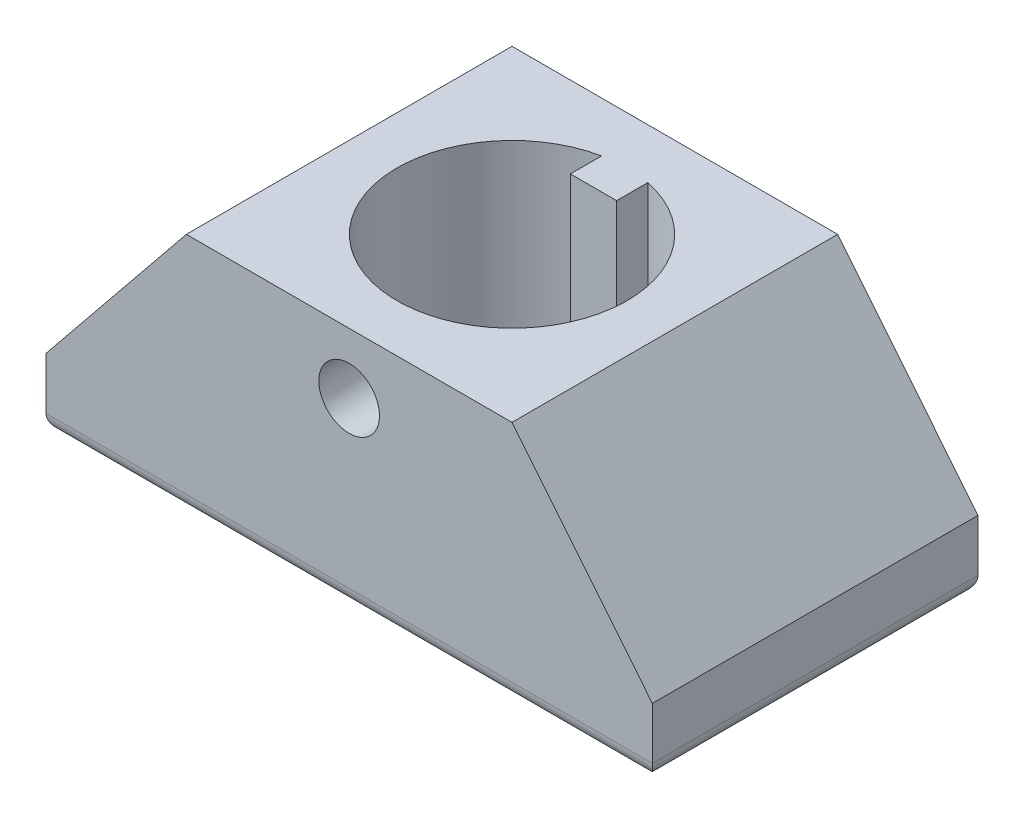
SolidWorks part; units mm, degrees
ref_plane "Front Plane" through (0, 0, 0) normal (0, 0, 1) x (1, 0, 0)
ref_plane "Top Plane" through (0, 0, 0) normal (0, 1, 0) x (1, 0, 0)
ref_plane "Right Plane" through (0, 0, 0) normal (1, 0, 0) x (0, 0, -1)
sketch "Sketch1" plane through (0, 0, 0) normal (0, 1, 0) x (1, 0, 0)
  line L0 (-1.335, 6.5044) -> (-1.335, 4.7044)
  line L1 (-1.335, 4.7044) -> (1.335, 4.7044)
  line L2 (1.335, 4.7044) -> (1.335, 6.5044)
  line L4 (-9.4, -9.4) -> (9.4, -9.4)
  line L5 (-9.4, -9.4) -> (-9.4, 9.4)
  line L6 (-9.4, 9.4) -> (9.4, 9.4)
  line L7 (9.4, -9.4) -> (9.4, 9.4)
  line L8 (-9.4, -9.4) -> (9.4, 9.4) construction
  line L9 (-9.4, 9.4) -> (9.4, -9.4) construction
  arc A1 (-1.335, 6.5044) -> (1.335, 6.5044) centre (0, 0) ccw
  dimension "D1" = 13.28
  dimension "D2" = 18.8
  dimension "D3" = 1.8
  dimension "D4" = 2.67
  dimension "D5" = 1.335
  dimension "D6" = 18.8
extrude "Boss-Extrude1" add sketch "Sketch1" along normal blind 10
sketch "Sketch5" plane through (0, 0, -4.7044) normal (0, 0, 1) x (1, 0, 0)
  line L1 (1.335, 10) -> (-1.335, 10) construction
  circle A0 centre (-0.0001, 6.5) radius 1.75
  dimension "D1" = 3.5
  dimension "D2" = 3.5
extrude "Cut-Extrude3" cut sketch "Sketch5" along normal blind 15
sketch "Sketch6" plane through (0, 0, 0) normal (0, -1, 0) x (1, 0, 0)
  line L1 (17.5, -9.4) -> (-17.5, -9.4)
  line L2 (17.5, -9.4) -> (17.5, 9.4)
  line L3 (17.5, 9.4) -> (-17.5, 9.4)
  line L4 (-17.5, -9.4) -> (-17.5, 9.4)
  line L5 (17.5, -9.4) -> (-17.5, 9.4) construction
  line L6 (17.5, 9.4) -> (-17.5, -9.4) construction
  point P0 (0, 0)
  dimension "D1" = 18.8
  dimension "D2" = 35
extrude "Boss-Extrude2" add sketch "Sketch6" along normal blind 4
sketch "Sketch7" plane through (0, 0, 9.4) normal (0, 0, 1) x (1, 0, 0)
  line L0 (-9.4, 10) -> (-9.4, 0)
  line L1 (-9.4, 0) -> (-17.5, 0)
  line L2 (-17.5, 0) -> (-9.4, 10)
  line L3 (9.4, 0) -> (17.5, 0)
  line L4 (17.5, 0) -> (9.4, 10)
  line L5 (9.4, 10) -> (9.4, 0)
extrude "Boss-Extrude3" add sketch "Sketch7" against normal up to surface (18.8 mm away) up to face at (-1.0125, 2.75, -9.4)
fillet "Fillet4" radius 1 4 edges at (17.5, -4, 0) (0, -4, -9.4) (-17.5, -4, 0) (0, -4, 9.4)
sketch "Sketch8" plane through (0, 0, 0) normal (0, 1, 0) x (1, 0, 0)
  line L0 (1.335, 4.7044) -> (-1.335, 4.7044) construction
  line L1 (1.335, 6.5044) -> (1.335, 4.7044) construction
  line L2 (-1.335, 4.7044) -> (-1.335, 6.5044) construction
  line L3 (1.335, 4.7044) -> (-1.335, 4.7044)
  line L4 (1.335, 6.5044) -> (1.335, 4.7044)
  line L5 (-1.335, 4.7044) -> (-1.335, 6.5044)
  arc A0 (-1.335, 6.5044) -> (1.335, 6.5044) centre (0, 0) ccw construction
  arc A1 (-1.335, 6.5044) -> (1.335, 6.5044) centre (0, 0) ccw
extrude "Cut-Extrude4" cut sketch "Sketch8" against normal blind 4
fillet "Fillet5" radius 0.5 4 edges at (-1.335, -4, -5.6044) (0, -4, -4.7044) (1.335, -4, -5.6044) (0, -4, 6.64)
equation "\"CageLeftBottomEdge\"=22.11mm"
equation "\"CageLeftTopEdge\"=22.11mm"
equation "\"CageRightBottomEdge\"=21.63mm"
equation "\"CageRightTopEdge\"=21.63mm"
equation "\"CageHeight\"=86.04mm"
equation "\"CageLength\"=73.76mm"
equation "\"CageTopScrewClearance\"=10mm"
equation "\"CageBottomScrewClearance\"=25mm"
equation "\"CageLeftTopDepth\"= 11.65mm"
equation "\"CageLeftBottomDepth\"=11.11mm"
equation "\"CageLeftTopHeight\"=8.56175mm"
equation "\"CageLeftBottomHeight\"=16mm"
equation "\"CageRightTopDepth\"= 11.05mm"
equation "\"CageRightBottomDepth\"=10.58mm"
equation "\"CageRightTopHeight\"=9.6mm"
equation "\"CageRightBottomHeight\"=15.49mm"
equation "\"CageLeftTopChannelDepth\"=2.41908mm"
equation "\"CageLeftBottomChannelDepth\"=2.588mm"
equation "\"CageLeftChannelHeight\"=11.7mm"
equation "\"CageRightTopChannelDepth\"=2.32mm"
equation "\"CageRightBottomChannelDepth\"=2.318mm"
equation "\"CageRightChannelHeight\"=10mm"
equation "\"CageChanRelHeight\"=23.99mm"
equation "\"CageChanRelDepth\"=5.492mm"
equation "\"CageChamberRadius\"=16.261mm"
equation "\"CageScrewDiameter\"=4.8mm"
equation "\"CageSetScrewDiameter\"=3.5mm"
equation "\"CageAxleRadius\"=6.639mm"
equation "\"CageAxleKeyHeight\"=1.619mm"
equation "\"CageAxleKeyWidth\"=2.662mm"
equation "\"CageHoseWindowWidth\"=16.29mm"
equation "\"CageHoseWindowHeight\"=26.5mm"
equation "\"CageHoseWindow-Edge\"=8.89mm"
equation "\"CageScrew-VerticalEdge\"=5.0mm"
equation "\"CageScrew-HorizontalEdge\"=7.5mm"
equation "\"CageScrew-HoseCornerScrewEdge\"=4.45mm"
equation "\"CageAxle-BottomEdge\"=56.05mm"
equation "\"CageAxle-FrontEdge\"=46.03mm"
equation "\"CageBackSetScrew-Axle\"=40mm"
equation "\"CageFrontSetScrew-Axle\"=22mm"
equation "\"CageVelocityWindow-BackEdge\"=34.8mm"
equation "\"CageVelocityWindow-BottomEdge\"=27.55mm"
equation "\"CageVelocityWindowHeight\"=22.29mm"
equation "\"CageVelocityWindowWidth\"=12.61mm"
equation "\"TriggerSlot-BottomEdge\"=6.35mm"
equation "\"TriggerSlot-FrontEdge\"=15mm"
equation "\"TriggerSlotSize\"=6.7mm"
equation "\"TriggerRackOffset\"=.236224in"
equation "\"TriggerSlotSizeInt\"=.25in"
equation "\"MotorMountLegLength\"=.25in"
equation "\"GearOffset\"=.264907in"
equation "\"TriggerSlotSpacing\"=.25in"
equation "\"TriggerMiniSlotWidth\"=3.5mm"
equation "\"TriggerRackWidth\"=6.5mm"
equation "\"whitemotordepth\"=11.27mm"
equation "\"whitemotorbackdepth\"=3.845mm"
equation "\"whitemotoraxledepth\" = 3.5mm"
equation "\"whitemotoraxleoffset\"=11.4mm"
equation "\"whitemotorwidth\"=12.07mm"
equation "\"whitemotorheight\"=16.68mm"
equation "\"whitemotorcylinderlength\" =13.04mm"
equation "\"whitemotorcylinderradius\"=3.845mm"
equation "\"whitemotorcylinderoffset\"=2.35mm"
equation "\"whitemotorcutoutlength\"=1.88mm"
equation "\"whitemotorouterrad\"=5mm"
equation "\"whitemotorinnerrad\"=2.95mm"
equation "\"elasticracklength\"=2in"
equation "\"elasticrackpegsize\"=.25in"
equation "\"elasticrackpegbuffer\"=.125in"
equation "\"elasticrackpegspacing\"=1.76476378in"
equation "\"elasticbaybuffer\"=.25in"
equation "\"elasticdepth\"=.125in"
equation "\"elasticbaydepth\"=.75in"
equation "\"motormountwidth\"=12mm"
equation "\"motormountcornerfillet\"=3mm"
equation "\"pandiscradius\"=14in"
equation "\"towermaterialwidth\"=.25in"
equation "\"towerslotlength\"=.5in"
equation "\"towermarkerspace\"=5in"
equation "\"towerslothorizoffset\"=1in"
equation "\"towerslothorizspacing\"=2in"
equation "\"towerslotvertoffset\"=3in"
equation "\"towerslotvertspacing\"=1in"
equation "\"towerheight\"=12in"
equation "\"towerupslot\"=1in"
equation "\"toweraxle\"=.5in"
equation "\"stepperouterrad\"=10mm"
equation "\"stepperscrewsize\"=3.45mm"
equation "\"stepperscrewc2c\"=49.5mm"
equation "\"stepperdepthoffset\"=24mm"
equation "\"stepperhorizoffset\"=22.91mm"
equation "\"shaftslotOD\"=18.8mm"
equation "\"shaftslotID\"=13.28mm"
equation "\"shaftkeywidth\"=2.67mm"
equation "\"shaftkeydepth\"=1.8mm"
equation "\"shaftcollartotaldepth\"=12.5mm"
equation "\"shaftsquaredepth\"=6mm"
equation "\"shaftsetscrewsize\"=3.5mm"
equation "\"shaftkeytightdepth\"=1.85mm"
equation "\"shaftslottightID\"=12.78mm"
equation "\"D3@Sketch1\"=\"shaftkeydepth\""
equation "\"D4@Sketch1\"=\"shaftkeywidth\""
equation "\"D5@Sketch1\"=\"shaftkeywidth\"/2"
equation "\"D1@Sketch1\"=\"shaftslotID\""
equation "\"D6@Sketch1\"=\"shaftslotOD\""
equation "\"D2@Sketch1\"=\"shaftslotOD\""
equation "\"D1@Sketch6\"=\"shaftslotOD\""
equation "\"cagecollartotaldepth\"=10mm"
equation "\"D1@Boss-Extrude1\"=\"cagecollartotaldepth\""
equation "\"D1@Sketch5\"=\"shaftsetscrewsize\""
equation "\"D2@Sketch5\"=\"shaftsetscrewsize\""
equation "\"cagecollartotalwidth\"=35mm"
equation "\"D2@Sketch6\"=\"cagecollartotalwidth\""
equation "\"cagecollarbasedepth\"=4mm"
equation "\"D1@Boss-Extrude2\"=\"cagecollarbasedepth\""
equation "\"shaftsetscrewoffset\"=9mm"
equation "\"gearhubintdiam\"=30mm"
equation "\"gearhubintwid\"=15mm"
equation "\"towerspeedwidth\"=2in"
equation "\"towerspeedheight\"=8in"
equation "\"towerspeedgap\"=2in"
equation "\"stepperaxleflat\"=.037in"
equation "\"stepperaxlerad\"=0.11811024in"
equation "\"ajaxaxlesize\"=3.87mm"
equation "\"ajaxinnercut\"=2.3mm"
equation "\"ajaxwidth\"=6.1mm"
equation "\"ajaxdiametral\"=25.8854"
equation "\"ajaxcutoutdepth\"=2.3mm"
equation "\"ajax4020gap\"=29.5mm"
equation "\"ajax4010gap\"=24.5mm"
equation "\"ajax20hubbuffer\"=6.1mm"
equation "\"ajax20hubholeoffset\"=.19685in"
equation "\"ajax20hubholesize\"=.059055in"
equation "\"ajax20cutoutint\"=13.4mm"
equation "\"ajax40hubholesize\"=7.21mm"
equation "\"ajax40hubholeoffset\"=10mm"
equation "\"ajax40hubbuffer\"=8.9mm"
equation "\"ajax40cutoutint\"=32.6mm"
equation "\"bearingpandiscrad\"=6.8in"
equation "\"bearingpandiscang\"=48.75deg"
equation "\"bearingclearholedist\"=4.7345in"
equation "\"bearingclearholesize\"=.5in"
equation "\"bearingclearholeang\"=22.5deg"
equation "\"bearingmountholedist\"=4.25in"
equation "\"bearingwirehole\"=1.5in"
equation "\"no6diam\"=.146in"
equation "\"shortconangle\"=20deg"
equation "\"shortconlen\"=.875in"
equation "\"longconlen\"=1.25in"
equation "\"longconangle\"=15deg"
